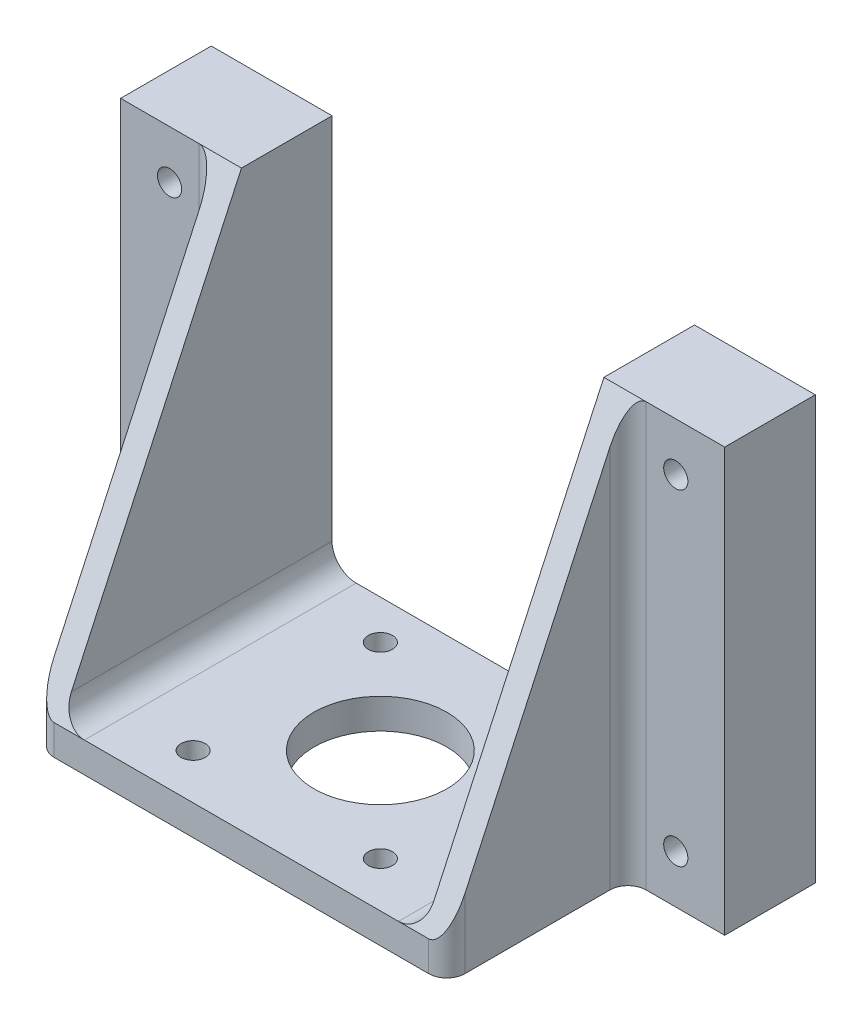
SolidWorks part; units mm, degrees
ref_plane "前视基准面" through (0, 0, 0) normal (0, 0, 1) x (1, 0, 0)
ref_plane "上视基准面" through (0, 0, 0) normal (0, 1, 0) x (1, 0, 0)
ref_plane "右视基准面" through (0, 0, 0) normal (1, 0, 0) x (0, 0, -1)
other "Configuration Table"
sketch "草图5" plane through (0, 0, 0) normal (0, 0, 1) x (1, 0, 0)
  line L0 (-41.9, 0) -> (0, 0)
  line L1 (-50, 35) -> (50, 35)
  line L2 (-50, 35) -> (-50, -35)
  line L3 (-50, -35) -> (50, -35)
  line L4 (50, 35) -> (50, -35)
  line L5 (-50, 35) -> (50, -35) construction
  line L6 (-50, -35) -> (50, 35) construction
  line L7 (-41.9, 27) -> (41.9, 27)
  line L8 (-41.9, 27) -> (-41.9, -27)
  line L9 (-41.9, -27) -> (41.9, -27)
  line L10 (41.9, 27) -> (41.9, -27)
  line L11 (-41.9, 27) -> (41.9, -27) construction
  line L12 (-41.9, -27) -> (41.9, 27) construction
  line L13 (0, 0) -> (0, 27)
  line L15 (-21, 35) -> (21, 35)
  line L17 (-21, -27) -> (21, -27)
  circle A0 centre (-41.9, 27) radius 2
  circle A1 centre (41.9, 27) radius 2
  circle A2 centre (41.9, -27) radius 2
  circle A3 centre (-41.9, -27) radius 2
  point P0 (0, 0)
  point P6 (0, 0)
  point P18 (0, 4)
  dimension "D5" = 0
  dimension "D1" = 100
  dimension "D2" = 70
  dimension "D3" = 8.1
  dimension "D4" = 8
extrude "凸台-拉伸10" add sketch "草图5" along normal blind 0.0001 contours L4 L1 L2 L3 L9 A3 L8 A0 L7 A1 L10 A2 | A0 L8 L0 L13 L7 | L8 A3 L9 A2 L10 A1 L7 L13 L0 region at (-20.894, 13.4648, 0) region at (6.9647, -4.4883, 0) region at (-35.5, 33.7793, 0)
sketch "草图6" plane through (0, 0, 0.0001) normal (0, 0, 1) x (1, 0, 0)
  line L0 (-50, -35) -> (50, -35) construction
  line L1 (-30, -30) -> (30, -30)
  line L2 (-30, -30) -> (-30, -35)
  line L3 (-30, -35) -> (30, -35)
  line L4 (30, -30) -> (30, -35)
  line L5 (-30, -30) -> (30, -35) construction
  line L6 (-30, -35) -> (30, -30) construction
  line L7 (0, -30) -> (0, -35)
  point P0 (0, -32.5)
  dimension "D1" = 60
  dimension "D2" = 5
extrude "凸台-拉伸11" add sketch "草图6" along normal blind 45 contours L1 L7 L3 L4 | L1 L4 L3 L2 region at (15, -32.5, 0.0001)
sketch "草图7" plane through (0, 0, 0.0001) normal (0, 0, 1) x (1, 0, 0)
  line L0 (0, 0) -> (0, -27)
  line L1 (-30, -35) -> (-34, -35)
  line L2 (-30, -35) -> (-30, 35)
  line L3 (-30, 35) -> (-34, 35)
  line L4 (-34, -35) -> (-34, 35)
  line L6 (30, 35) -> (34, 35)
  line L7 (34, -35) -> (34, 35)
  line L8 (30, -35) -> (34, -35)
  line L9 (30, -35) -> (30, 35)
  line M11 (30, -30) -> (30, -35)
  line M12 (30, -35) -> (50, -35)
  line M20 (-50, -35) -> (-30, -35)
  line M21 (-30, -35) -> (-30, -30)
  dimension "D1" = 4
  dimension "D2" = 70
extrude "凸台-拉伸12" add sketch "草图7" along normal blind 45 contours L4 L2 L3 M20 M21 | L9 L7 L6 M11 M12 region at (-32, 0, 0.0001) region at (32, 0, 0.0001)
sketch "草图8" plane through (-34, 0, 0) normal (-1, 0, 0) x (0, 0, 1)
  line L0 (45.0001, -30) -> (15.0001, 35)
  line L2 (15.0001, 35) -> (45.0001, 35)
  line L3 (45.0001, 35) -> (45.0001, -30)
  line L4 (45.0001, -35) -> (45.0001, 35) construction
  line L5 (45.0001, 35) -> (0.0001, 35) construction
  dimension "D1" = 0
  dimension "D2" = 15
extrude "切除-拉伸1" cut sketch "草图8" against normal blind 76
sketch "草图16" plane through (0, 0, 0.0001) normal (0, 0, 1) x (1, 0, 0)
  line L4 (50, 35) -> (34, 35)
  line L5 (34, 35) -> (34, -35)
  line L6 (34, -35) -> (50, -35)
  line L7 (50, -35) -> (50, 35)
  line L8 (50, 35) -> (34, 35)
  line L9 (34, 35) -> (34, -35)
  line L10 (34, -35) -> (50, -35)
  line L11 (50, -35) -> (50, 35)
  line L12 (-34, -35) -> (-34, 35)
  line L13 (-34, 35) -> (-50, 35)
  line L14 (-50, 35) -> (-50, -35)
  line L15 (-50, -35) -> (-34, -35)
  line L16 (-34, -35) -> (-34, 35)
  line L17 (-34, 35) -> (-50, 35)
  line L18 (-50, 35) -> (-50, -35)
  line L19 (-50, -35) -> (-34, -35)
  circle A1 centre (-41.9, 27) radius 2
  circle A3 centre (-41.9, -27) radius 2
  circle A4 centre (41.9, 27) radius 2 construction
  circle A5 centre (41.9, -27) radius 2 construction
  circle A6 centre (41.9, 27) radius 2
  circle A7 centre (41.9, -27) radius 2
  dimension "D1" = 0
  dimension "D2" = 0
extrude "凸台-拉伸16" add sketch "草图16" along normal blind 15 contours L8 L9 L10 L11 | L16 L17 L18 L19
extrude "切除-拉伸2" cut sketch "草图5<3>" along normal blind 49 contours L7 A0 L8 | L8 A0 L7 | A1 L10 L7 | A1 L7 L10 | L9 A2 L10 | L10 A2 L9 | A3 L9 L8 | A3 L8 L9 region at (-42.1829, 27.2829, 0) region at (-41.0512, 26.1512, 0) region at (-41.0512, -26.1512, 0) region at (-42.1829, -27.2829, 0) region at (42.1829, 27.2829, 0) region at (41.0512, 26.1512, 0) region at (42.1829, -27.2829, 0) region at (41.0512, -26.1512, 0)
sketch "草图5<3>" plane through (0, 0, 0) normal (0, 0, 1) x (1, 0, 0) same geometry as "草图5"
sketch "草图17" plane through (0, -35, 0) normal (0, -1, 0) x (1, 0, 0)
  line L1 (-15.5, 37.5) -> (15.5, 37.5)
  line L2 (-15.5, 37.5) -> (-15.5, 6.5)
  line L3 (-15.5, 6.5) -> (15.5, 6.5)
  line L4 (15.5, 37.5) -> (15.5, 6.5)
  line L5 (-15.5, 37.5) -> (15.5, 6.5)
  line L6 (15.5, 37.5) -> (-15.5, 6.5)
  line L7 (-15.5, 22) -> (0, 22)
  line L8 (0, 22) -> (0, 37.5)
  line L9 (-50, 0) -> (50, 0) construction
  circle A0 centre (-15.5, 37.5) radius 2
  circle A1 centre (15.5, 37.5) radius 2
  circle A2 centre (-15.5, 6.5) radius 2
  circle A3 centre (15.5, 6.5) radius 2
  circle A4 centre (0, 22) radius 11
  dimension "D1" = 6.5
  dimension "D2" = 31
  dimension "D3" = 31
extrude "切除-拉伸5" cut sketch "草图17" against normal through all contours L5 A4 L7 | L8 A4 L5 | L5 A4 L6 | L6 A4 L8 | L6 A4 L5 | L7 A4 L6 | A3 | A2 | A0 | A1 region at (-2.7348, -35, 28.6023) region at (-6.6023, -35, 24.7348) region at (2.7348, -35, 28.6023) region at (-6.6023, -35, 19.2652) region at (6.6023, -35, 22) region at (0, -35, 15.3977)
fillet "圆角1" radius 3 4 edges at (34, 0, 15.0001) (-34, 0, 15.0001) (-34, -32.5, 45.0001) (34, -32.5, 45.0001)
sketch "草图18" plane through (0, 0, 0.0001) normal (0, 0, 1) x (1, 0, 0)
  line L4 (30, -30) -> (30, 35)
  line L5 (30, 35) -> (-30, 35)
  line L6 (-30, 35) -> (-30, -30)
  line L7 (-30, -30) -> (30, -30)
  line L8 (30, -30) -> (30, 35)
  line L9 (30, 35) -> (-30, 35)
  line L10 (-30, 35) -> (-30, -30)
  line L11 (-30, -30) -> (30, -30)
  dimension "D1" = 0
extrude "切除-拉伸6" cut sketch "草图18" against normal through all
fillet "圆角2" radius 4 2 edges at (-30, -30, 22.5001) (30, -30, 22.5001)
